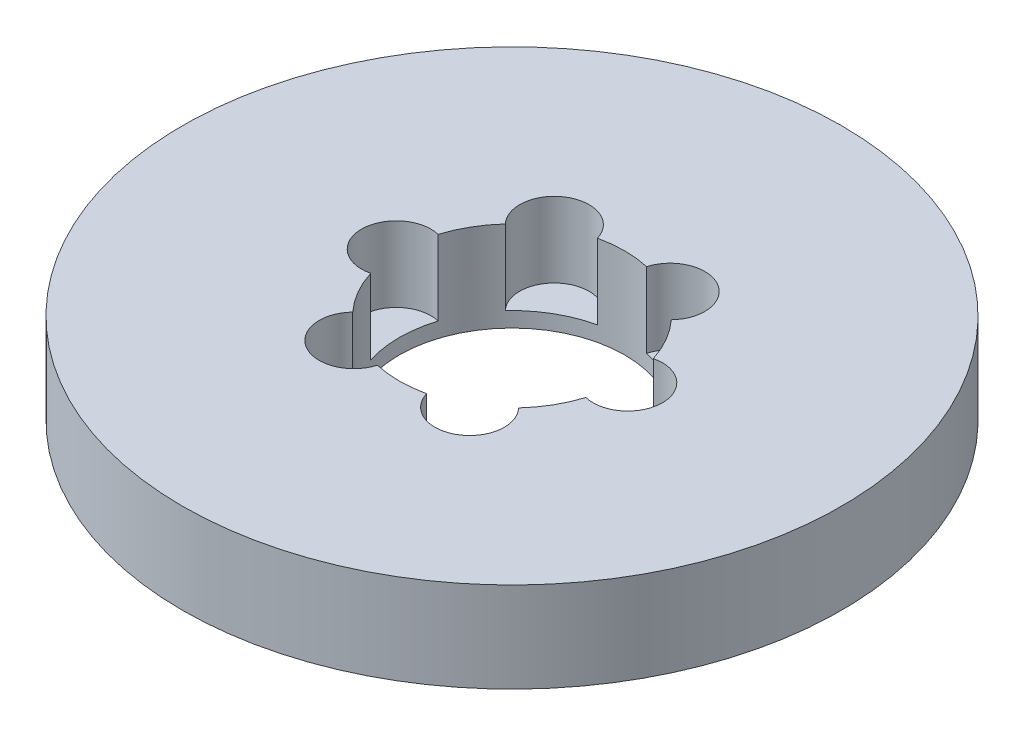
SolidWorks part; units mm, degrees
ref_plane "Front Plane" through (0, 0, 0) normal (0, 0, 1) x (1, 0, 0)
ref_plane "Top Plane" through (0, 0, 0) normal (0, 1, 0) x (1, 0, 0)
ref_plane "Right Plane" through (0, 0, 0) normal (1, 0, 0) x (0, 0, -1)
sketch "Sketch1" plane through (0, 0, 0) normal (0, 1, 0) x (1, 0, 0)
  circle A0 centre (0, 0) radius 95
  dimension "FLANGE_OD" = 190
extrude "Boss-Extrude1" add sketch "Sketch1" along normal blind 26
sketch "Sketch2" plane through (0, 0, 0) normal (0, 1, 0) x (1, 0, 0)
  circle A0 centre (0, 0) radius 32.5
  dimension "BORE_D" = 65
extrude "Cut-Extrude1" cut sketch "Sketch2" along normal through all
sketch "Sketch3" plane through (0, 26, 0) normal (0, 1, 0) x (1, 0, 0)
  circle A0 centre (0, 0) radius 33.3716 construction
  circle A1 centre (-33.3716, 0) radius 10
  dimension "BOLT_D" = 20
  dimension "BOLT_PCD" = 66.7432
extrude "Cut-Extrude2" cut sketch "Sketch3" against normal blind 21.6371
pattern_circular "CirPattern1" count 6 over 360 about axis through (0, 0, 0) along (0, 1, 0) of "Cut-Extrude2"
